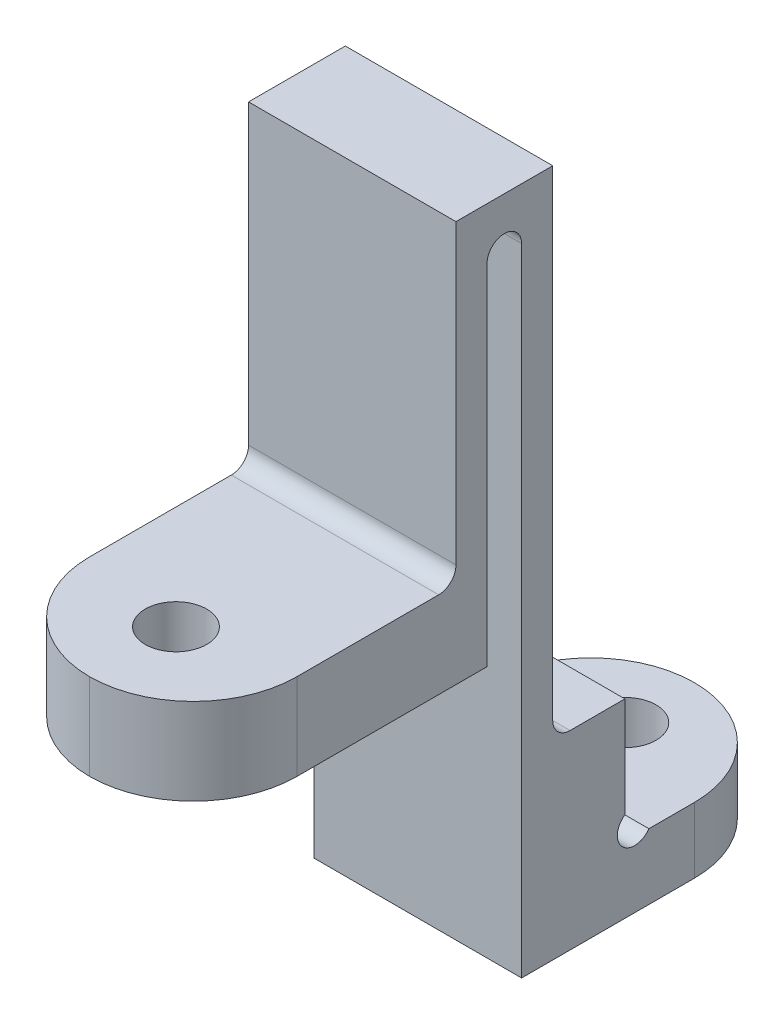
SolidWorks part; units mm, degrees
material "Copper"
ref_plane "Front Plane" through (0, 0, 0) normal (0, 0, 1) x (1, 0, 0)
ref_plane "Top Plane" through (0, 0, 0) normal (0, 1, 0) x (1, 0, 0)
ref_plane "Right Plane" through (0, 0, 0) normal (1, 0, 0) x (0, 0, -1)
ref_plane "Plane1" through (7.5, 0, 0) normal (1, 0, 0) x (0, 0, -1)
sketch "Sketch1" plane through (7.5, 0, 0) normal (1, 0, 0) x (0, 0, -1)
  line L1 (-10.5, 16.9976) -> (-10.5, 5.3976)
  line L2 (-10.5, 5.3976) -> (-2, 5.3976)
  line L3 (-2, 5.3976) -> (-2, 15.4976)
  line L4 (-1, -2.9024) -> (-1, 15.4976)
  line L7 (-1.5, 15.9976) -> (-1.5, 16.9976) construction
  line L10 (-1, -2.9024) -> (7, -2.9024)
  line L11 (7, -2.9024) -> (7, 16.9976)
  line L12 (7, 16.9976) -> (-10.5, 16.9976)
  arc A0 (-2, 15.4976) -> (-1, 15.4976) centre (-1.5, 15.4976) cw
  dimension "D1" = 10.1
  dimension "D2" = 1
  dimension "D3" = 1
  dimension "D4" = 8.5
  dimension "D5" = 8
  dimension "D6" = 18.9
extrude "Boss-Extrude1" add sketch "Sketch1" against normal blind 6
sketch "Sketch2" plane through (1.5, 0, 0) normal (-1, 0, 0) x (0, 0, 1)
  line L0 (0, 15.5) -> (0.001, 15.5)
  line L1 (0.001, 15.5) -> (0.001, 20.5)
  line L2 (0.001, 20.5) -> (0, 20.5)
  line L3 (0, 20.5) -> (0, 15.5)
extrude "Cut-Extrude1" [suppressed] cut sketch "Sketch2" against normal blind 7.5
sketch3d "3DSketch1" plane through (0, 0, 0) normal (0, 0, 1) x (1, 0, 0)
  dimension "D1" = 0.5
sketch "Sketch3" plane through (1.5, 0, 0) normal (-1, 0, 0) x (0, 0, 1)
  line L0 (2.9, 17.4976) -> (2.9, 10.3976)
  line L1 (2.9, 10.3976) -> (10.5, 10.3976)
  line L2 (10.5, 10.3976) -> (10.5, 17.4976)
  line L3 (10.5, 17.4976) -> (2.9, 17.4976)
  line L4 (1.5, 20.4976) -> (1.5, 19.5006) construction
  line L5 (1, -2.9024) -> (-7, -2.9024) construction
  line L6 (-7.5, 17.4976) -> (0.1, 17.4976)
  line L7 (-7.5, 2.5976) -> (-7.5, 17.4976)
  line L8 (0.1, 2.5976) -> (-7.5, 2.5976)
  line L9 (0.1, 17.4976) -> (0.1, 2.5976)
  line L10 (-7, 16.9976) -> (10.5, 16.9976) construction
  line L12 (10.5, 5.3976) -> (2, 5.3976) construction
  dimension "D3" = 7.6
  dimension "D4" = 5.5
  dimension "D5" = 0.5
  dimension "D6" = 5
extrude "Cut-Extrude2" cut sketch "Sketch3" against normal through all
sketch "Sketch4" plane through (1.5, 0, 0) normal (-1, 0, 0) x (0, 0, 1)
  line L0 (10.5, 10.3976) -> (2.9, 10.3976)
  line L1 (2.9, 10.3976) -> (10.5, 10.3976) construction
  line L2 (2.9, 10.3976) -> (2.9, 7.8976)
  line L3 (2.9, 7.8976) -> (10.5, 7.8976)
  line L4 (1.5, 20.4976) -> (1.5, 15.9976) construction
  line L5 (-1.9863, -1.0024) -> (-1.9863, 2.5976)
  line L6 (-7.4863, 2.5976) -> (-1.9863, 2.5976)
  line L7 (-7.4863, -1.0024) -> (-7.4863, 2.5976)
  line L8 (-1.9863, -1.0024) -> (-7.4863, -1.0024)
  line L10 (-7, 2.5976) -> (0.1, 2.5976) construction
  line L11 (10.5, 10.3976) -> (10.5, 5.3976) construction
  line L12 (10.5, 7.8976) -> (10.5, 10.3976)
  line L14 (-1.9863, 2.5976) -> (-1.9863, -1.0024) construction
  line L15 (0.1, 2.5976) -> (0.1, 16.9976) construction
  line L16 (10.5, 5.3976) -> (2, 5.3976) construction
  arc A0 (2, 15.4976) -> (1, 15.4976) centre (1.5, 15.4976) ccw construction
  dimension "D1" = 3.6
  dimension "D2" = 0
  dimension "D4" = 7.6
  dimension "D5" = 5.5
  dimension "D6" = 2.5
  dimension "D7" = 2.0863
extrude "Cut-Extrude3" cut sketch "Sketch4" against normal through all
sketch "Sketch5" plane through (1.5, 0, 0) normal (-1, 0, 0) x (0, 0, 1)
  line L0 (1, 4.5) -> (0.999, 4.5)
  line L1 (0.999, 4.5) -> (0.999, 0.5)
  line L2 (0.999, 0.5) -> (1, 0.5)
  line L3 (1, 0.5) -> (1, 4.5)
extrude "Cut-Extrude4" [suppressed] cut sketch "Sketch5" against normal blind 7.5
sketch "Sketch6" plane through (1.5, 0, 0) normal (-1, 0, 0) x (0, 0, 1)
  line L0 (0, 0.5) -> (0.001, 0.5)
  line L1 (0.001, 0.5) -> (0.001, 4.5)
  line L2 (0.001, 4.5) -> (0, 4.5)
  line L3 (0, 4.5) -> (0, 0.5)
extrude "Cut-Extrude5" [suppressed] cut sketch "Sketch6" against normal blind 7.5
hole_wizard "#30 (0.1285) Diameter Hole1" [suppressed] positions "Sketch8" profile "Sketch7" hole size "#30" standard "ANSI Inch"
sketch "Sketch8" [suppressed] plane through (0, 0, 0.001) normal (0, 0, -1) x (-1, 0, 0)
  point P0 (-3.75, 2.5)
sketch "Sketch7" plane through (3.75, 2.5, 0.001) normal (1, 0, 0) x (0, 1, 0)
  line L0 (0, 0) -> (0, 10.499)
  line L1 (0, 10.499) -> (1.6319, 10.499)
  line L2 (1.6319, 10.499) -> (1.6319, 0)
  line L5 (1.6319, 0) -> (0, 0)
  line L11 (0, -6.35) -> (0, 107.95) construction
  dimension "Thru Hole Dia." = 3.2639
  dimension "Thru Hole Depth" = 10.499
fillet "Fillet1" [suppressed] radius 0.5
fillet "Fillet2" radius 3 4 edges at (1.5, 6.6476, 10.5) (7.5, 6.6476, 10.5) (7.5, -1.9524, -7) (1.5, -1.9524, -7) tangent propagation no
hole_wizard "#2-56 Tapped Hole1" positions "Sketch11" profile "Sketch12" tap size "#2-56" standard "ANSI Inch" end condition through all
sketch "Sketch11" plane through (0, 7.8976, 0) normal (0, 1, 0) x (1, 0, 0)
  line L6 (4.5, 7) -> (4.5, -10.5) construction
  point P35 (4.5, -8)
  dimension "D2" = 2.5
sketch "Sketch12" plane through (4.5, 7.8976, 8) normal (1, 0, 0) x (0, 0, 1)
  line L0 (0, 0) -> (0, 10.8)
  line L1 (0, 10.8) -> (0.889, 10.8)
  line L2 (0.889, 10.8) -> (0.889, 0)
  line L5 (0.889, 0) -> (0, 0)
  line L11 (0, -6.35) -> (0, 107.95) construction
  dimension "Thread Major Dia." = 1.778
  dimension "Thru Tap Drill Depth" = 10.8
fillet "Fillet3" radius 0.5 2 edges at (4.5, 2.5976, 0.1) (4.5, 7.8976, 2.9)
hole_wizard "#2-56 Tapped Hole2" positions "Sketch17" profile "Sketch18" tap size "#2-56" standard "ANSI Inch" end condition through all
sketch "Sketch17" plane through (0, -1.0024, 0) normal (0, 1, 0) x (1, 0, 0)
  line L0 (4.5, 1.9863) -> (4.5, 7) construction
  line L4 (7.5, 1.9863) -> (1.5, 1.9863) construction
  point P0 (4.5, 5)
  dimension "D1" = 2
sketch "Sketch18" plane through (4.5, -1.0024, -5) normal (1, 0, 0) x (0, 0, 1)
  line L0 (0, 0) -> (0, 1.9)
  line L1 (0, 1.9) -> (0.889, 1.9)
  line L2 (0.889, 1.9) -> (0.889, 0)
  line L5 (0.889, 0) -> (0, 0)
  line L11 (0, -6.35) -> (0, 107.95) construction
  dimension "Thread Major Dia." = 1.778
  dimension "Thru Tap Drill Depth" = 1.9
sketch "Sketch19" plane through (7.5, 0, 0) normal (1, 0, 0) x (0, 0, -1)
  line L0 (1.9863, -1.0024) -> (2.2691, -0.7196) construction
  line L1 (1.9863, -1.0024) -> (1.9863, 2.5976) construction
  circle A0 centre (2.2691, -0.7196) radius 0.5
  dimension "D1" = 0.4
  dimension "D3" = 1
  dimension "D2" = 45
extrude "Cut-Extrude6" cut sketch "Sketch19" against normal through all
